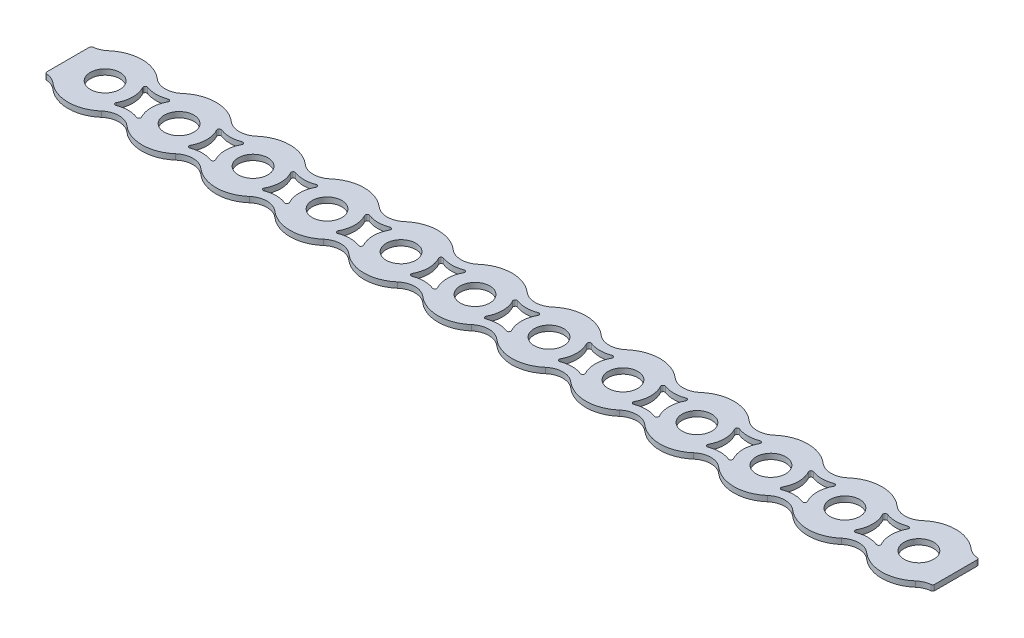
SolidWorks part; units mm, degrees
ref_plane "Front Plane" through (0, 0, 0) normal (0, 0, 1) x (1, 0, 0)
ref_plane "Top Plane" through (0, 0, 0) normal (0, 1, 0) x (1, 0, 0)
ref_plane "Right Plane" through (0, 0, 0) normal (1, 0, 0) x (0, 0, -1)
ref_axis "X Axis" through (-88.99, 0, 0) along (1, 0, 0)
ref_axis "Y Axis" through (0, 55, 0) along (0, -1, 0)
ref_axis "Z Axis" through (0, 0, -88.99) along (0, 0, 1)
sketch "Sketch1" plane through (0, 0, 0) normal (0, 1, 0) x (1, 0, 0)
  line L0 (4, 4) -> (4, -4) construction
  line L5 (0, -2.5) -> (4, -2.5) construction
  line L6 (0, 0) -> (8, 0) construction
  line L7 (0, 2.5) -> (0, -2.5)
  line L8 (96, 2.5) -> (96, -2.5)
  line L9 (8, 2.5) -> (8, -2.5) construction
  circle A1 centre (4, 0) radius 1.6
  arc A12 (1.3699, -3.0137) -> (6.6301, -3.0137) centre (4, 0) ccw
  arc A13 (0, -2.5) -> (1.3699, -3.0137) centre (0, -4.5833) cw
  arc A14 (0, 2.5) -> (1.3699, 3.0137) centre (0, 4.5833) ccw
  arc A15 (8, 2.5) -> (6.6301, 3.0137) centre (8, 4.5833) cw
  arc A16 (8, -2.5) -> (6.6301, -3.0137) centre (8, -4.5833) ccw
  arc A17 (6.6301, 3.0137) -> (1.3699, 3.0137) centre (4, 0) ccw
  arc A18 (8, 2.5) -> (9.3699, 3.0137) centre (8, 4.5833) ccw
  arc A19 (14.6301, 3.0137) -> (9.3699, 3.0137) centre (12, 0) ccw
  arc A20 (16, 2.5) -> (14.6301, 3.0137) centre (16, 4.5833) cw
  arc A21 (16, -2.5) -> (14.6301, -3.0137) centre (16, -4.5833) ccw
  arc A22 (9.3699, -3.0137) -> (14.6301, -3.0137) centre (12, 0) ccw
  arc A23 (8, -2.5) -> (9.3699, -3.0137) centre (8, -4.5833) cw
  circle A24 centre (12, 0) radius 1.6
  arc A25 (16, 2.5) -> (17.3699, 3.0137) centre (16, 4.5833) ccw
  arc A26 (22.6301, 3.0137) -> (17.3699, 3.0137) centre (20, 0) ccw
  arc A27 (24, 2.5) -> (22.6301, 3.0137) centre (24, 4.5833) cw
  arc A28 (24, -2.5) -> (22.6301, -3.0137) centre (24, -4.5833) ccw
  arc A29 (17.3699, -3.0137) -> (22.6301, -3.0137) centre (20, 0) ccw
  arc A30 (16, -2.5) -> (17.3699, -3.0137) centre (16, -4.5833) cw
  circle A31 centre (20, 0) radius 1.6
  arc A32 (24, 2.5) -> (25.3699, 3.0137) centre (24, 4.5833) ccw
  arc A33 (30.6301, 3.0137) -> (25.3699, 3.0137) centre (28, 0) ccw
  arc A34 (32, 2.5) -> (30.6301, 3.0137) centre (32, 4.5833) cw
  arc A35 (32, -2.5) -> (30.6301, -3.0137) centre (32, -4.5833) ccw
  arc A36 (25.3699, -3.0137) -> (30.6301, -3.0137) centre (28, 0) ccw
  arc A37 (24, -2.5) -> (25.3699, -3.0137) centre (24, -4.5833) cw
  circle A38 centre (28, 0) radius 1.6
  arc A39 (32, 2.5) -> (33.3699, 3.0137) centre (32, 4.5833) ccw
  arc A40 (38.6301, 3.0137) -> (33.3699, 3.0137) centre (36, 0) ccw
  arc A41 (40, 2.5) -> (38.6301, 3.0137) centre (40, 4.5833) cw
  arc A42 (40, -2.5) -> (38.6301, -3.0137) centre (40, -4.5833) ccw
  arc A43 (33.3699, -3.0137) -> (38.6301, -3.0137) centre (36, 0) ccw
  arc A44 (32, -2.5) -> (33.3699, -3.0137) centre (32, -4.5833) cw
  circle A45 centre (36, 0) radius 1.6
  arc A46 (40, 2.5) -> (41.3699, 3.0137) centre (40, 4.5833) ccw
  arc A47 (46.6301, 3.0137) -> (41.3699, 3.0137) centre (44, 0) ccw
  arc A48 (48, 2.5) -> (46.6301, 3.0137) centre (48, 4.5833) cw
  arc A49 (48, -2.5) -> (46.6301, -3.0137) centre (48, -4.5833) ccw
  arc A50 (41.3699, -3.0137) -> (46.6301, -3.0137) centre (44, 0) ccw
  arc A51 (40, -2.5) -> (41.3699, -3.0137) centre (40, -4.5833) cw
  circle A52 centre (44, 0) radius 1.6
  arc A53 (48, 2.5) -> (49.3699, 3.0137) centre (48, 4.5833) ccw
  arc A54 (54.6301, 3.0137) -> (49.3699, 3.0137) centre (52, 0) ccw
  arc A55 (56, 2.5) -> (54.6301, 3.0137) centre (56, 4.5833) cw
  arc A56 (56, -2.5) -> (54.6301, -3.0137) centre (56, -4.5833) ccw
  arc A57 (49.3699, -3.0137) -> (54.6301, -3.0137) centre (52, 0) ccw
  arc A58 (48, -2.5) -> (49.3699, -3.0137) centre (48, -4.5833) cw
  circle A59 centre (52, 0) radius 1.6
  arc A60 (56, 2.5) -> (57.3699, 3.0137) centre (56, 4.5833) ccw
  arc A61 (62.6301, 3.0137) -> (57.3699, 3.0137) centre (60, 0) ccw
  arc A62 (64, 2.5) -> (62.6301, 3.0137) centre (64, 4.5833) cw
  arc A63 (64, -2.5) -> (62.6301, -3.0137) centre (64, -4.5833) ccw
  arc A64 (57.3699, -3.0137) -> (62.6301, -3.0137) centre (60, 0) ccw
  arc A65 (56, -2.5) -> (57.3699, -3.0137) centre (56, -4.5833) cw
  circle A66 centre (60, 0) radius 1.6
  arc A67 (64, 2.5) -> (65.3699, 3.0137) centre (64, 4.5833) ccw
  arc A68 (70.6301, 3.0137) -> (65.3699, 3.0137) centre (68, 0) ccw
  arc A69 (72, 2.5) -> (70.6301, 3.0137) centre (72, 4.5833) cw
  arc A70 (72, -2.5) -> (70.6301, -3.0137) centre (72, -4.5833) ccw
  arc A71 (65.3699, -3.0137) -> (70.6301, -3.0137) centre (68, 0) ccw
  arc A72 (64, -2.5) -> (65.3699, -3.0137) centre (64, -4.5833) cw
  circle A73 centre (68, 0) radius 1.6
  arc A74 (72, 2.5) -> (73.3699, 3.0137) centre (72, 4.5833) ccw
  arc A75 (78.6301, 3.0137) -> (73.3699, 3.0137) centre (76, 0) ccw
  arc A76 (80, 2.5) -> (78.6301, 3.0137) centre (80, 4.5833) cw
  arc A77 (80, -2.5) -> (78.6301, -3.0137) centre (80, -4.5833) ccw
  arc A78 (73.3699, -3.0137) -> (78.6301, -3.0137) centre (76, 0) ccw
  arc A79 (72, -2.5) -> (73.3699, -3.0137) centre (72, -4.5833) cw
  circle A80 centre (76, 0) radius 1.6
  arc A81 (80, 2.5) -> (81.3699, 3.0137) centre (80, 4.5833) ccw
  arc A82 (86.6301, 3.0137) -> (81.3699, 3.0137) centre (84, 0) ccw
  arc A83 (88, 2.5) -> (86.6301, 3.0137) centre (88, 4.5833) cw
  arc A84 (88, -2.5) -> (86.6301, -3.0137) centre (88, -4.5833) ccw
  arc A85 (81.3699, -3.0137) -> (86.6301, -3.0137) centre (84, 0) ccw
  arc A86 (80, -2.5) -> (81.3699, -3.0137) centre (80, -4.5833) cw
  circle A87 centre (84, 0) radius 1.6
  arc A88 (88, 2.5) -> (89.3699, 3.0137) centre (88, 4.5833) ccw
  arc A89 (94.6301, 3.0137) -> (89.3699, 3.0137) centre (92, 0) ccw
  arc A90 (96, 2.5) -> (94.6301, 3.0137) centre (96, 4.5833) cw
  arc A91 (96, -2.5) -> (94.6301, -3.0137) centre (96, -4.5833) ccw
  arc A92 (89.3699, -3.0137) -> (94.6301, -3.0137) centre (92, 0) ccw
  arc A93 (88, -2.5) -> (89.3699, -3.0137) centre (88, -4.5833) cw
  circle A94 centre (92, 0) radius 1.6
  dimension "D3" = 3.2
  dimension "D1" = 4
  dimension "D4" = 5
  dimension "D5" = 12
extrude "Boss-Extrude1" add sketch "Sketch1" along normal blind 0.6 contours A56 A65 A64 A63 A62 A61 A60 A55 A54 A53 A48 A47 A46 A41 A40 A39 A34 A33 A32 A27 A26 A25 A20 A19 A18 A15 A17 A14 L7 A13 A12 A16 A23 A22 A21 A30 A29 A28 A37 A36 A35 A44 A43 A42 A51 A50 A49 A58 A57 region at (48, 0, 0)
sketch "Sketch2" plane through (0, 0, 0) normal (0, 1, 0) x (1, 0, 0)
  line L2 (0, 0) -> (8, 0) construction
  line L3 (0, 0) -> (8, 0) construction
  circle A27 centre (92, 0) radius 1.6 construction
  circle A28 centre (84, 0) radius 1.6 construction
  circle A29 centre (76, 0) radius 1.6 construction
  circle A30 centre (68, 0) radius 1.6 construction
  circle A31 centre (60, 0) radius 1.6 construction
  circle A32 centre (52, 0) radius 1.6 construction
  circle A33 centre (44, 0) radius 1.6 construction
  circle A34 centre (36, 0) radius 1.6 construction
  circle A35 centre (28, 0) radius 1.6 construction
  circle A36 centre (20, 0) radius 1.6 construction
  circle A37 centre (12, 0) radius 1.6 construction
  circle A38 centre (4, 0) radius 1.6 construction
  circle A39 centre (92, 0) radius 1.6 construction
  circle A40 centre (84, 0) radius 1.6 construction
  circle A41 centre (76, 0) radius 1.6 construction
  circle A42 centre (68, 0) radius 1.6 construction
  circle A43 centre (60, 0) radius 1.6 construction
  circle A44 centre (52, 0) radius 1.6 construction
  circle A45 centre (44, 0) radius 1.6 construction
  circle A46 centre (36, 0) radius 1.6 construction
  circle A47 centre (28, 0) radius 1.6 construction
  circle A48 centre (20, 0) radius 1.6 construction
  circle A49 centre (12, 0) radius 1.6 construction
  circle A50 centre (4, 0) radius 1.6 construction
  circle A51 centre (92, 0) radius 3
  circle A52 centre (84, 0) radius 3
  circle A53 centre (76, 0) radius 3
  circle A54 centre (68, 0) radius 3
  circle A55 centre (60, 0) radius 3
  circle A56 centre (52, 0) radius 3
  circle A57 centre (44, 0) radius 3
  circle A58 centre (36, 0) radius 3
  circle A59 centre (28, 0) radius 3
  circle A60 centre (20, 0) radius 3
  circle A61 centre (12, 0) radius 3
  circle A62 centre (4, 0) radius 3
  arc A63 (6.6301, 3.0137) -> (1.3699, 3.0137) centre (4, 0) ccw construction
  arc A64 (5.9726, 2.2603) -> (10.0274, 2.2603) centre (8, 4.5833) ccw
  arc A65 (5.9726, -2.2603) -> (10.0274, -2.2603) centre (8, -4.5833) cw
  arc A67 (6.6301, 3.0137) -> (8, 2.5) centre (8, 4.5833) ccw construction
  arc A68 (13.9726, 2.2603) -> (18.0274, 2.2603) centre (16, 4.5833) ccw
  arc A69 (13.9726, -2.2603) -> (18.0274, -2.2603) centre (16, -4.5833) cw
  arc A70 (21.9726, 2.2603) -> (26.0274, 2.2603) centre (24, 4.5833) ccw
  arc A71 (21.9726, -2.2603) -> (26.0274, -2.2603) centre (24, -4.5833) cw
  arc A72 (29.9726, 2.2603) -> (34.0274, 2.2603) centre (32, 4.5833) ccw
  arc A73 (29.9726, -2.2603) -> (34.0274, -2.2603) centre (32, -4.5833) cw
  arc A74 (37.9726, 2.2603) -> (42.0274, 2.2603) centre (40, 4.5833) ccw
  arc A75 (37.9726, -2.2603) -> (42.0274, -2.2603) centre (40, -4.5833) cw
  arc A76 (45.9726, 2.2603) -> (50.0274, 2.2603) centre (48, 4.5833) ccw
  arc A77 (45.9726, -2.2603) -> (50.0274, -2.2603) centre (48, -4.5833) cw
  arc A78 (53.9726, 2.2603) -> (58.0274, 2.2603) centre (56, 4.5833) ccw
  arc A79 (53.9726, -2.2603) -> (58.0274, -2.2603) centre (56, -4.5833) cw
  arc A80 (61.9726, 2.2603) -> (66.0274, 2.2603) centre (64, 4.5833) ccw
  arc A81 (61.9726, -2.2603) -> (66.0274, -2.2603) centre (64, -4.5833) cw
  arc A82 (69.9726, 2.2603) -> (74.0274, 2.2603) centre (72, 4.5833) ccw
  arc A83 (69.9726, -2.2603) -> (74.0274, -2.2603) centre (72, -4.5833) cw
  arc A84 (77.9726, 2.2603) -> (82.0274, 2.2603) centre (80, 4.5833) ccw
  arc A85 (77.9726, -2.2603) -> (82.0274, -2.2603) centre (80, -4.5833) cw
  arc A86 (85.9726, 2.2603) -> (90.0274, 2.2603) centre (88, 4.5833) ccw
  arc A87 (85.9726, -2.2603) -> (90.0274, -2.2603) centre (88, -4.5833) cw
  dimension "D1" = 1
  dimension "D2" = 1
extrude "Cut-Extrude1" cut sketch "Sketch2" along normal through all contours A52 A51 | A51 | A53 A85 A52 A84 | A54 A83 A53 A82 | A55 A81 A54 A80 | A56 A79 A55 A78 | A62 A65 A61 A64 | A61 A69 A60 A68 | A60 A71 A59 A70 | A59 A73 A58 A72 | A58 A75 A57 A74 | A57 A77 A56 A76 region at (88, 0, 0) region at (80, 0, 0) region at (72, 0, 0) region at (64, 0, 0) region at (56, 0, 0) region at (48, 0, 0) region at (40, 0, 0) region at (32, 0, 0) region at (24, 0, 0) region at (16, 0, 0) region at (8, 0, 0)
fillet "Fillet1" radius 0.2 48 edges at (0, 0.3, -2.5) (0, 0.3, 2.5) (85.9726, 0.3, 2.2603) (90.0274, 0.3, 2.2603) (90.0274, 0.3, -2.2603) (85.9726, 0.3, -2.2603) (37.9726, 0.3, 2.2603) (42.0274, 0.3, 2.2603) (42.0274, 0.3, -2.2603) (37.9726, 0.3, -2.2603) (21.9726, 0.3, 2.2603) (26.0274, 0.3, 2.2603) (26.0274, 0.3, -2.2603) (21.9726, 0.3, -2.2603) (5.9726, 0.3, 2.2603) (10.0274, 0.3, 2.2603) (10.0274, 0.3, -2.2603) (5.9726, 0.3, -2.2603) (61.9726, 0.3, 2.2603) (66.0274, 0.3, 2.2603) (66.0274, 0.3, -2.2603) (61.9726, 0.3, -2.2603) (77.9726, 0.3, 2.2603) (82.0274, 0.3, 2.2603) (82.0274, 0.3, -2.2603) (77.9726, 0.3, -2.2603) (96, 0.3, -2.5) (96, 0.3, 2.5) (69.9726, 0.3, 2.2603) (74.0274, 0.3, 2.2603) (74.0274, 0.3, -2.2603) (69.9726, 0.3, -2.2603) (53.9726, 0.3, 2.2603) (58.0274, 0.3, 2.2603) (58.0274, 0.3, -2.2603) (53.9726, 0.3, -2.2603) (13.9726, 0.3, 2.2603) (18.0274, 0.3, 2.2603) (18.0274, 0.3, -2.2603) (13.9726, 0.3, -2.2603) (29.9726, 0.3, 2.2603) (34.0274, 0.3, 2.2603) (34.0274, 0.3, -2.2603) (29.9726, 0.3, -2.2603) (45.9726, 0.3, 2.2603) (50.0274, 0.3, 2.2603) (50.0274, 0.3, -2.2603) (45.9726, 0.3, -2.2603)
other "Flex2" [suppressed] parameters "D0"=550, "D1"=6, "D2"=0
